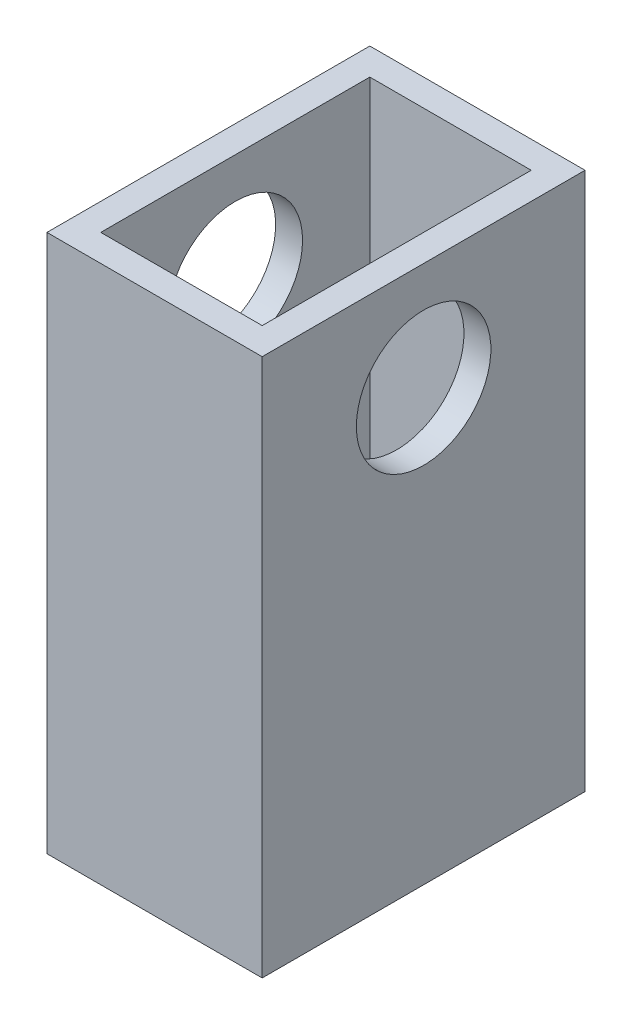
SolidWorks part; units mm, degrees
material "ABS"
ref_plane "Front Plane" through (0, 0, 0) normal (0, 0, 1) x (1, 0, 0)
ref_plane "Top Plane" through (0, 0, 0) normal (0, 1, 0) x (1, 0, 0)
ref_plane "Right Plane" through (0, 0, 0) normal (1, 0, 0) x (0, 0, -1)
sketch "Sketch2" plane through (0, 0, 0) normal (0, 1, 0) x (1, 0, 0)
  line L0 (0, 0) -> (-40, 0)
  line L1 (0, 0) -> (0, -60)
  line L2 (-40, 0) -> (-40, -60)
  line L3 (0, -60) -> (-40, -60)
  dimension "D1" = 40
  dimension "D2" = 60
extrude "Boss-Extrude1" add sketch "Sketch2" along normal blind 100
sketch "Sketch3" plane through (-40, 0, 0) normal (-1, 0, 0) x (0, 0, 1)
  line L0 (30, 100) -> (30, 80) construction
  line L1 (0, 100) -> (60, 100) construction
  circle A0 centre (30, 80) radius 12.5
  dimension "D2" = 25
  dimension "D1" = 20
shell "Shell1" thickness 5 removed face at (-20, 0, 30) removed face at (-20, 100, 30)
extrude "Cut-Extrude1" cut sketch "Sketch3" against normal blind 100
